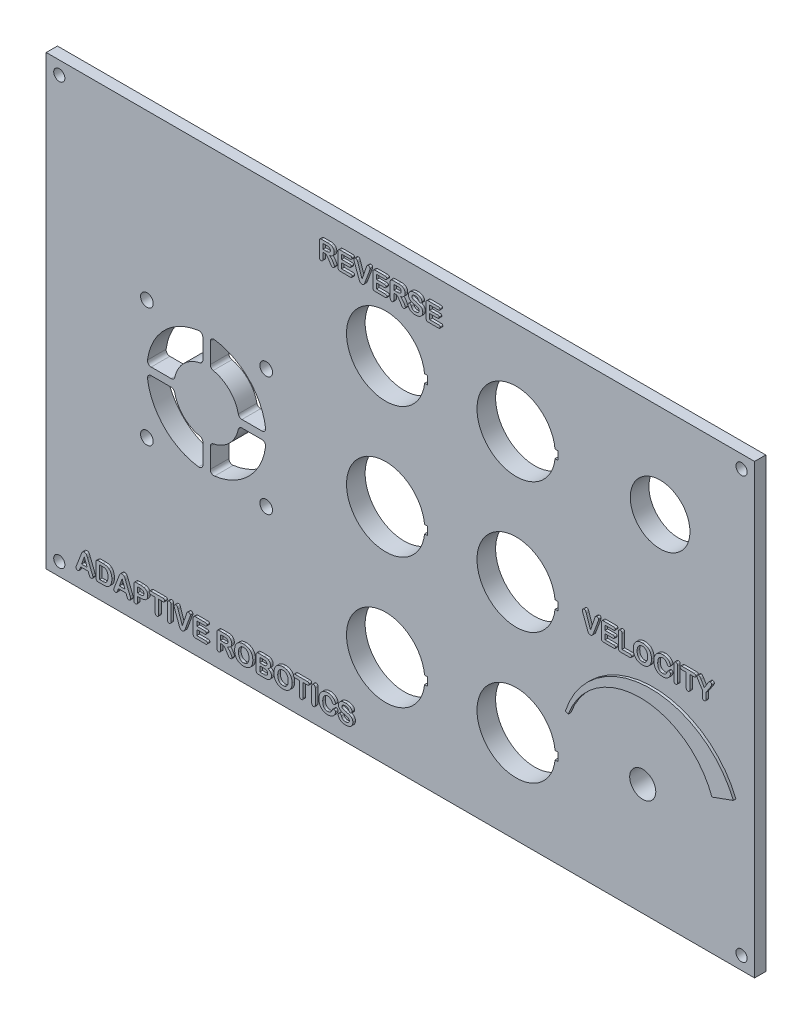
SolidWorks part; units mm, degrees
ref_plane "Front Plane" through (0, 0, 0) normal (0, 0, 1) x (1, 0, 0)
ref_plane "Top Plane" through (0, 0, 0) normal (0, 1, 0) x (1, 0, 0)
ref_plane "Right Plane" through (0, 0, 0) normal (1, 0, 0) x (0, 0, -1)
sketch "Sketch1" plane through (0, 0, 0) normal (0, 0, 1) x (1, 0, 0)
  line L0 (-3.9587, -60) -> (-3.9587, 60) construction
  line L1 (-95, -60) -> (95, -60)
  line L2 (-95, -60) -> (-95, 60)
  line L3 (-95, 60) -> (95, 60)
  line L4 (95, -60) -> (95, 60)
  line L5 (-95, -60) -> (95, 60) construction
  line L6 (-95, 60) -> (95, -60) construction
  line L7 (31.0413, -60) -> (31.0413, 60) construction
  line L8 (-95, 0) -> (95, 0) construction
  line L9 (-3.9587, 35) -> (31.0413, 35) construction
  line L10 (-21, 47.4067) -> (-83, 47.4067) construction
  line L11 (-21, 47.4067) -> (-21, -56.5933) construction
  line L12 (-21, -56.5933) -> (-83, -56.5933) construction
  line L13 (-83, 47.4067) -> (-83, -56.5933) construction
  line L14 (-3.9587, -35) -> (31.0413, -35) construction
  line L15 (-52, 47.4067) -> (-52, -56.5933) construction
  line L16 (-68, -16) -> (-36, -16) construction
  line L17 (-68, -16) -> (-68, 16) construction
  line L18 (-68, 16) -> (-36, 16) construction
  line L19 (-36, -16) -> (-36, 16) construction
  line L20 (-53, 8.6454) -> (-53, 15.9543)
  line L21 (-51, 8.6454) -> (-51, 15.9543)
  line L22 (-43.3546, 1) -> (-36.0457, 1)
  line L23 (-43.3546, -1) -> (-36.0457, -1)
  line L24 (-51, -8.6454) -> (-51, -15.9543)
  line L25 (-53, -8.6454) -> (-53, -15.9543)
  line L26 (-60.6454, -1) -> (-67.9543, -1)
  line L27 (-60.6454, 1) -> (-67.9543, 1)
  line L28 (7.2913, 33.9) -> (7.2913, 36.1)
  line L29 (7.2913, 36.1) -> (6.4835, 36.1)
  line L30 (7.2913, 33.9) -> (6.4835, 33.9)
  line L31 (42.2913, 36.1) -> (41.4835, 36.1)
  line L32 (42.2913, 33.9) -> (42.2913, 36.1)
  line L33 (42.2913, 33.9) -> (41.4835, 33.9)
  line L34 (42.2913, 1.1) -> (41.4835, 1.1)
  line L35 (42.2913, -1.1) -> (42.2913, 1.1)
  line L36 (42.2913, -1.1) -> (41.4835, -1.1)
  line L37 (42.2913, -33.9) -> (41.4835, -33.9)
  line L38 (42.2913, -36.1) -> (42.2913, -33.9)
  line L39 (42.2913, -36.1) -> (41.4835, -36.1)
  line L40 (7.2913, 1.1) -> (6.4835, 1.1)
  line L41 (7.2913, -1.1) -> (7.2913, 1.1)
  line L42 (7.2913, -1.1) -> (6.4835, -1.1)
  line L43 (7.2913, -33.9) -> (6.4835, -33.9)
  line L44 (7.2913, -36.1) -> (7.2913, -33.9)
  line L45 (7.2913, -36.1) -> (6.4835, -36.1)
  circle A0 centre (-91.5, 56.5) radius 1.5
  circle A1 centre (91.5, 56.5) radius 1.5
  circle A2 centre (91.5, -56.5) radius 1.5
  circle A3 centre (-91.5, -56.5) radius 1.5
  arc A4 (6.4835, 36.1) -> (6.4835, 33.9) centre (-3.9587, 35) ccw
  arc A5 (6.4835, 1.1) -> (6.4835, -1.1) centre (-3.9587, 0) ccw
  arc A6 (6.4835, -33.9) -> (6.4835, -36.1) centre (-3.9587, -35) ccw
  arc A7 (41.4835, 36.1) -> (41.4835, 33.9) centre (31.0413, 35) ccw
  arc A8 (41.4835, 1.1) -> (41.4835, -1.1) centre (31.0413, 0) ccw
  arc A9 (41.4835, -33.9) -> (41.4835, -36.1) centre (31.0413, -35) ccw
  circle A10 centre (69.6607, 35) radius 8
  circle A11 centre (65, -30) radius 3.5
  circle A12 centre (69.6607, 35) radius 15 construction
  circle A13 centre (-36, 16) radius 1.7
  circle A14 centre (-36, -16) radius 1.7
  circle A15 centre (-68, -16) radius 1.7
  circle A16 centre (-68, 16) radius 1.7
  arc A17 (-67.9543, -1) -> (-53, -15.9543) centre (-52, 0) ccw
  arc A18 (-60.6454, -1) -> (-53, -8.6454) centre (-52, 0) ccw
  arc A19 (-53, 8.6454) -> (-60.6454, 1) centre (-52, 0) ccw
  arc A20 (-53, 15.9543) -> (-67.9543, 1) centre (-52, 0) ccw
  arc A21 (-43.3546, 1) -> (-51, 8.6454) centre (-52, 0) ccw
  arc A22 (-36.0457, 1) -> (-51, 15.9543) centre (-52, 0) ccw
  arc A23 (-51, -8.6454) -> (-43.3546, -1) centre (-52, 0) ccw
  arc A24 (-51, -15.9543) -> (-36.0457, -1) centre (-52, 0) ccw
  circle A25 centre (65, -30) radius 10 construction
  point P0 (0, 0)
  point P47 (-52, 16)
  point P52 (-36, 0)
  point P61 (7.2913, 35)
  point P75 (-52, 0)
  dimension "D3" = 3
  dimension "D4" = 3.5
  dimension "D5" = 3.5
  dimension "D8" = 3.5
  dimension "D9" = 3.5
  dimension "D10" = 3.5
  dimension "D11" = 21
  dimension "D12" = 35
  dimension "D15" = 16
  dimension "D16" = 7
  dimension "D17" = 30
  dimension "D18" = 30
  dimension "D19" = 30
  dimension "D22" = 3.4
  dimension "D26" = 0.75
  dimension "D30" = 20
  dimension "D1" = 190
  dimension "D2" = 120
  dimension "D13" = 62
  dimension "D14" = 104
  dimension "D20" = 32
  dimension "D21" = 12
  dimension "D23" = 2
  dimension "D25" = 2.2
  dimension "D27" = 35
  dimension "D6" = 2
  dimension "D7" = 2
  dimension "D28" = 2
  dimension "D29" = 3
  dimension "D24" = 4
extrude "Boss-Extrude1" add sketch "Sketch1" along normal blind 5
sketch "Sketch5" plane through (0, 0, 0) normal (0, 0, 1) x (1, 0, 0)
  line L1 (-95, 60) -> (95, 60)
  line L2 (-95, 60) -> (-95, -60)
  line L3 (-95, -60) -> (95, -60)
  line L4 (95, 60) -> (95, -60)
  line L38 (-87.5, 57.5) -> (87.5, 57.5)
  line L39 (87.5, 57.5) -> (87.5, 52.5)
  line L40 (92.5, 52.5) -> (87.5, 52.5)
  line L41 (92.5, 52.5) -> (92.5, -52.5)
  line L42 (92.5, -52.5) -> (87.5, -52.5)
  line L43 (87.5, -57.5) -> (87.5, -52.5)
  line L44 (-87.5, -57.5) -> (87.5, -57.5)
  line L45 (-87.5, -57.5) -> (-87.5, -52.5)
  line L46 (-92.5, -52.5) -> (-87.5, -52.5)
  line L47 (-92.5, 52.5) -> (-92.5, -52.5)
  line L48 (-92.5, 52.5) -> (-87.5, 52.5)
  line L49 (-87.5, 57.5) -> (-87.5, 52.5)
  dimension "D2" = 190
extrude "Cut-Extrude3" cut sketch "Sketch5" against normal blind 1 and the other way blind 2
fillet "Fillet1" radius 1 16 edges at (-51, -15.9543, 2.5) (-53, 8.6454, 2.5) (-67.9543, 1, 2.5) (-36.0457, -1, 2.5) (-43.3546, -1, 2.5) (-51, -8.6454, 2.5) (-53, -8.6454, 2.5) (-60.6454, -1, 2.5) (-60.6454, 1, 2.5) (-53, -15.9543, 2.5) (-36.0457, 1, 2.5) (-43.3546, 1, 2.5) (-51, 8.6454, 2.5) (-51, 15.9543, 2.5) (-53, 15.9543, 2.5) (-67.9543, -1, 2.5)
sketch "Sketch7" plane through (0, 0, 5) normal (0, 0, 1) x (1, 0, 0)
  line L0 (48.7389, -30) -> (111.4894, -30) construction
  line L1 (45.7363, -22.9886) -> (44.9378, -22.698)
  line L2 (65, -3.6036) -> (65, -63.1961) construction
  line L3 (84.2637, -22.9886) -> (90.0071, -20.8982)
  arc A2 (84.2637, -22.9886) -> (45.7363, -22.9886) centre (65, -30) ccw
  arc A3 (90.0071, -20.8982) -> (44.9378, -22.698) centre (67.8, -30) ccw
  text T0 "REVERSE" font "Arial Rounded MT Bold" height in points 20
  text T1 "VELOCITY" font "Arial Rounded MT Bold" height in points 20
  text T2 "ADAPTIVE ROBOTICS" font "Arial Rounded MT Bold" height in points 20
  dimension "D1" = 41
  dimension "D2" = 48
  dimension "D3" = 2.8
  dimension "D4" = 20
extrude "Boss-Extrude3" add sketch "Sketch7" along normal blind 0.7
